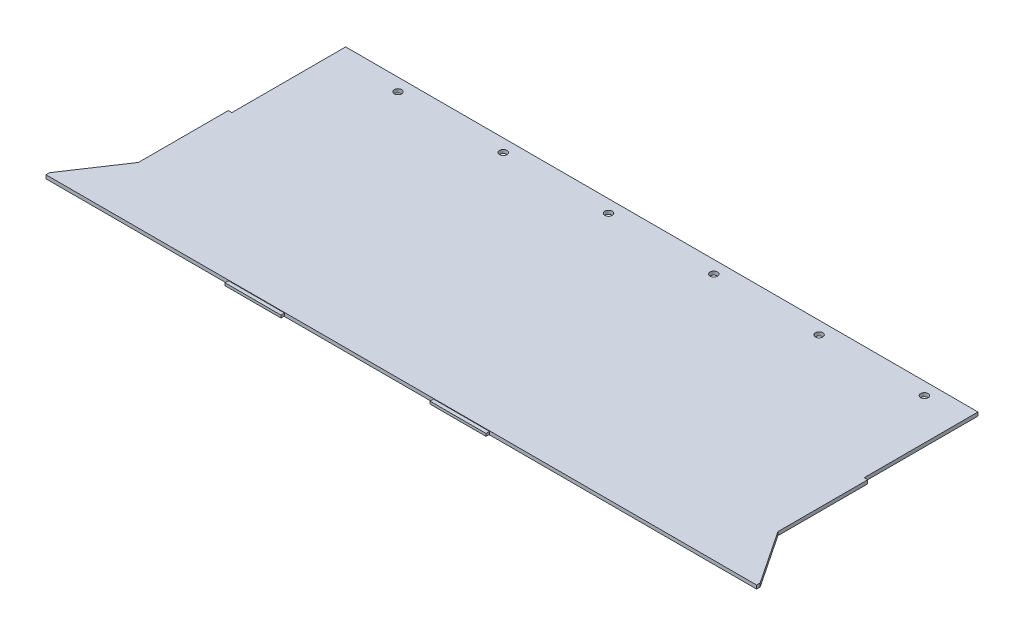
SolidWorks part; units mm, degrees
material "Custom Plastic"
ref_plane "X-Y Datum" through (0, 0, 0) normal (0, 0, 1) x (1, 0, 0)
ref_plane "X-Z Datum" through (0, 0, 0) normal (0, 1, 0) x (1, 0, 0)
ref_plane "Y-Z Datum" through (0, 0, 0) normal (1, 0, 0) x (0, 0, -1)
sketch "Sketch1" plane through (0, 0, 0) normal (0, 0, 1) x (1, 0, 0)
  line L1 (-285.4305, -1.5875) -> (285.4305, -1.5875)
  line L2 (-285.4305, -1.5875) -> (-285.4305, 1.5875)
  line L3 (-285.4305, 1.5875) -> (285.4305, 1.5875)
  line L4 (285.4305, -1.5875) -> (285.4305, 1.5875)
  line L5 (-285.4305, -1.5875) -> (285.4305, 1.5875) construction
  line L6 (-285.4305, 1.5875) -> (285.4305, -1.5875) construction
  point P0 (0, 0)
  dimension "D1" = 570.861
  dimension "D2" = 3.175
extrude "Boss-Extrude1" add sketch "Sketch1" along normal blind 232.6
sketch "Sketch2" plane through (0, 1.5875, 0) normal (0, 1, 0) x (1, 0, 0)
  line L0 (-176.5505, -181.8) -> (-285.4305, -181.8) construction
  line L1 (-285.4305, -232.6) -> (-285.4305, 0) construction
  line L3 (285.4305, -232.6) -> (-285.4305, -232.6) construction
  line L4 (-178.0615, -232.6) -> (-174.8865, -232.6)
  line L6 (-178.0615, -118.3) -> (-174.8865, -118.3)
  line L8 (-178.0615, -232.6) -> (-174.8865, -232.6)
  line L9 (-178.0615, -232.6) -> (-178.0615, -118.3)
  line L10 (-178.0615, -118.3) -> (-174.8865, -118.3)
  line L11 (-174.8865, -232.6) -> (-174.8865, -118.3)
  line L17 (-178.0615, -118.3) -> (-174.8865, -118.3)
  line L38 (-285.4305, 0) -> (-282.2555, 0)
  line L39 (-285.4305, 0) -> (-285.4305, -101.6)
  line L40 (-285.4305, -101.6) -> (-282.2555, -101.6)
  line L41 (-282.2555, 0) -> (-282.2555, -101.6)
  line L42 (285.4305, 0) -> (282.2555, 0)
  line L43 (285.4305, 0) -> (285.4305, -101.6)
  line L44 (285.4305, -101.6) -> (282.2555, -101.6)
  line L45 (282.2555, 0) -> (282.2555, -101.6)
  line M3 (285.4305, 0) -> (-285.4305, 0)
  line M4 (-285.4305, 0) -> (-285.4305, -232.6)
  line M6 (285.4305, -232.6) -> (285.4305, 0)
  dimension "D2" = 50.8
  dimension "D3" = 3.175
  dimension "D6" = 3.175
  dimension "D7" = 101.6
  dimension "D4" = 114.3
  dimension "D8" = 3.175
  dimension "D9" = 101.6
sketch "Sketch6" plane through (0, 0, 232.6) normal (0, 0, 1) x (1, 0, 0)
  line L14 (78.762, -1.143) -> (78.762, 1.143)
  line L15 (28.762, 1.143) -> (78.762, 1.143)
  line L16 (28.762, -1.143) -> (78.762, 1.143) construction
  line L17 (28.762, 1.143) -> (78.762, -1.143) construction
  line L18 (28.762, -1.143) -> (78.762, -1.143)
  line L19 (28.762, -1.143) -> (28.762, 1.143)
  line L20 (-104.238, -1.143) -> (-104.238, 1.143)
  line L21 (-154.238, 1.143) -> (-104.238, 1.143)
  line L22 (-154.238, -1.143) -> (-104.238, 1.143) construction
  line L23 (-154.238, 1.143) -> (-104.238, -1.143) construction
  line L24 (-154.238, -1.143) -> (-104.238, -1.143)
  line L25 (-154.238, -1.143) -> (-154.238, 1.143)
  point P6 (237.7325, 0)
  dimension "D2" = 50
sketch "Sketch7" plane through (0, -1.5875, 0) normal (0, -1, 0) x (-1, 0, 0)
  line L1 (-285.4305, -232.6) -> (-285.4305, 0) construction
  circle A2 centre (-245.6805, -11.2916) radius 3.302
  dimension "D1" = 39.75
  dimension "D2" = 6.604
extrude "Cut-Extrude4" cut sketch "Sketch7" against normal through all contours A2 region at (245.6805, -1.5875, 11.2916)
extrude "Boss-Extrude2" add sketch "Sketch6" along normal blind 3.175
pattern_linear "LPattern1" count 6 spacing 93.98 along (-1, 0, 0) of "Cut-Extrude4"
extrude "Cut-Extrude5" cut sketch "Sketch2" against normal through all contours L41 L40 M3 M4 | L45 L44 M3 M6 region at (283.843, 1.5875, 50.8) region at (-283.843, 1.5875, 50.8)
sketch "Sketch12" plane through (0, 1.5875, 0) normal (0, 1, 0) x (1, 0, 0)
  line L0 (-285.4305, -232.6) -> (-285.4305, -101.6) construction
  line L1 (-285.4305, -232.6) -> (-285.4305, -181.8)
  line L2 (285.4305, -232.6) -> (285.4305, -101.6) construction
  line L3 (285.4305, -232.6) -> (285.4305, -101.6)
  line L4 (-285.4305, -232.6) -> (-317.1805, -232.6)
  line L6 (-317.1805, -232.6) -> (-317.1805, -229.425)
  line L7 (-317.1805, -229.425) -> (-285.4305, -181.8)
  line M9 (-285.4305, -101.6) -> (-285.4305, -232.6)
  dimension "D1" = 31.75
  dimension "D2" = 50.8
  dimension "D3" = 3.175
extrude "Boss-Extrude3" add sketch "Sketch12" against normal blind 3.175 contours L4 M9 region at (-296.6364, 1.5875, 215.6044)
mirror "Mirror1" about plane through (0, 0, 0) normal (1, 0, 0) of "Boss-Extrude3"
